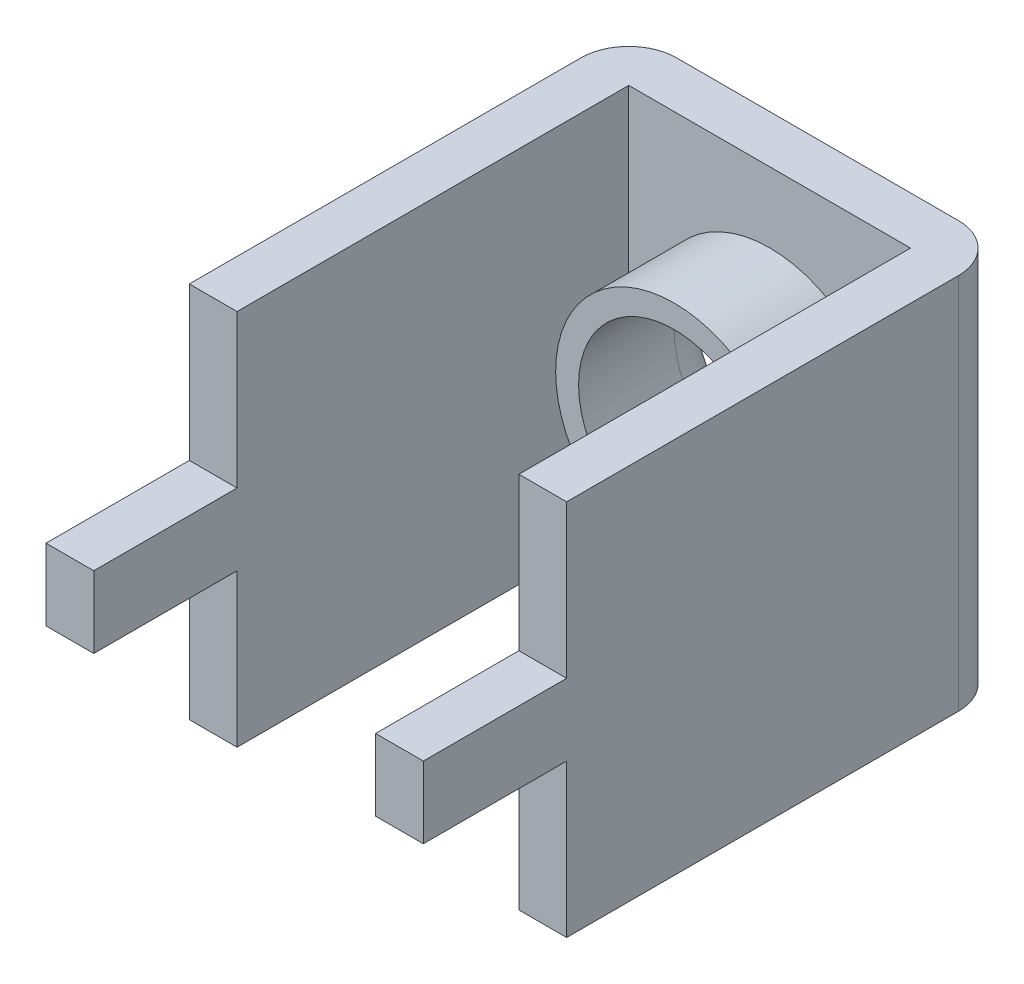
SolidWorks part; units mm, degrees
ref_plane "前视基准面" through (0, 0, 0) normal (0, 0, 1) x (1, 0, 0)
ref_plane "上视基准面" through (0, 0, 0) normal (0, 1, 0) x (1, 0, 0)
ref_plane "右视基准面" through (0, 0, 0) normal (1, 0, 0) x (0, 0, -1)
sketch "草图1" plane through (0, 0, 0) normal (0, 0, 1) x (1, 0, 0)
  line L1 (-3.95, -3.95) -> (3.95, -3.95)
  line L2 (-3.95, -3.95) -> (-3.95, 3.95)
  line L3 (-3.95, 3.95) -> (3.95, 3.95)
  line L4 (3.95, -3.95) -> (3.95, 3.95)
  line L5 (-3.95, -3.95) -> (3.95, 3.95) construction
  line L6 (-3.95, 3.95) -> (3.95, -3.95) construction
  circle A0 centre (0, 0) radius 2
  point P0 (0, 0)
  dimension "D3" = 4
  dimension "D1" = 7.9
  dimension "D2" = 7.9
extrude "凸台-拉伸1" add sketch "草图1" along normal blind 1
sketch "草图2" plane through (0, 0, 0) normal (0, 0, 1) x (1, 0, 0)
  line L0 (-3.95, -3.95) -> (3.95, -3.95) construction
  line L1 (-3.95, 3.95) -> (-2.95, 3.95)
  line L2 (-3.95, 3.95) -> (-3.95, -3.95)
  line L3 (-3.95, -3.95) -> (-2.95, -3.95)
  line L4 (-2.95, 3.95) -> (-2.95, -3.95)
  line L6 (3.95, 3.95) -> (2.95, 3.95)
  line L7 (3.95, 3.95) -> (3.95, -3.95)
  line L8 (3.95, -3.95) -> (2.95, -3.95)
  line L9 (2.95, 3.95) -> (2.95, -3.95)
  dimension "D1" = 1
extrude "凸台-拉伸2" add sketch "草图2" along normal blind 9.2
sketch "草图3" plane through (0, 0, 9.2) normal (0, 0, 1) x (1, 0, 0)
  line L0 (-3.95, 0) -> (3.95, 0) construction
  line L1 (-3.95, 3.95) -> (-3.95, -3.95) construction
  line L2 (3.95, -3.95) -> (3.95, 3.95) construction
  line L3 (-3.95, -0.75) -> (-3.95, 0.75)
  line L4 (-3.95, 0.75) -> (-2.95, 0.75)
  line L5 (-2.95, -3.95) -> (-2.95, 3.95) construction
  line L6 (-2.95, 0.75) -> (-2.95, -0.75)
  line L7 (-2.95, -0.75) -> (-3.95, -0.75)
  line L8 (0, 3.95) -> (0, -3.95) construction
  line L9 (2.95, 3.95) -> (-2.95, 3.95) construction
  line L10 (-2.95, -3.95) -> (2.95, -3.95) construction
  line L11 (2.95, 0.75) -> (2.95, -0.75)
  line L12 (3.95, 0.75) -> (2.95, 0.75)
  line L13 (3.95, -0.75) -> (3.95, 0.75)
  line L14 (2.95, -0.75) -> (3.95, -0.75)
  point P8 (-3.95, 0)
  dimension "D1" = 1.5
  dimension "D2" = 1
extrude "凸台-拉伸3" add sketch "草图3" along normal blind 3
sketch "草图4" plane through (0, 0, 1) normal (0, 0, 1) x (1, 0, 0)
  circle A0 centre (0, 0) radius 2
  circle A1 centre (0, 0) radius 2.4802
extrude "凸台-拉伸4" add sketch "草图4" along normal blind 2
fillet "圆角2" radius 1 3 edges at (2, 0, 0) (3.95, 0, 0) (-3.95, 0, 0)
